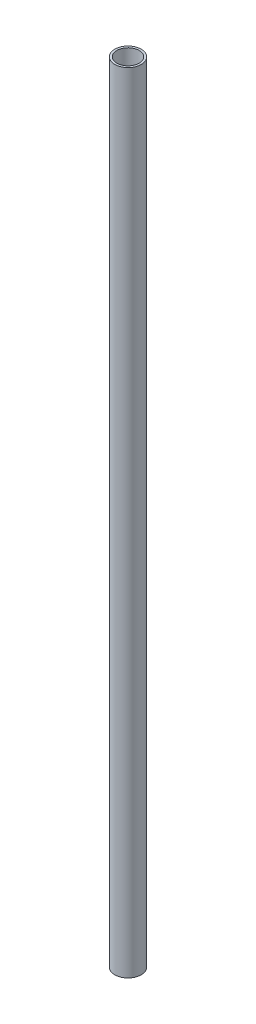
SolidWorks part; units mm, degrees
ref_plane "Front Plane" through (0, 0, 0) normal (0, 0, 1) x (1, 0, 0)
ref_plane "Top Plane" through (0, 0, 0) normal (0, 1, 0) x (1, 0, 0)
ref_plane "Right Plane" through (0, 0, 0) normal (1, 0, 0) x (0, 0, -1)
sketch "Sketch1" plane through (0, 0, 0) normal (0, 1, 0) x (1, 0, 0)
  circle A0 centre (0, 0) radius 7.75
  circle A1 centre (0, 0) radius 6.5
  dimension "D1" = 15.5
  dimension "D2" = 13
extrude "Boss-Extrude1" add sketch "Sketch1" along normal blind 441
extrude "Boss-Extrude3" add sketch "Sketch1<2>" against normal blind 20.4764
sketch "Sketch1<2>" plane through (0, 0, 0) normal (0, 1, 0) x (1, 0, 0) same geometry as "Sketch1"
